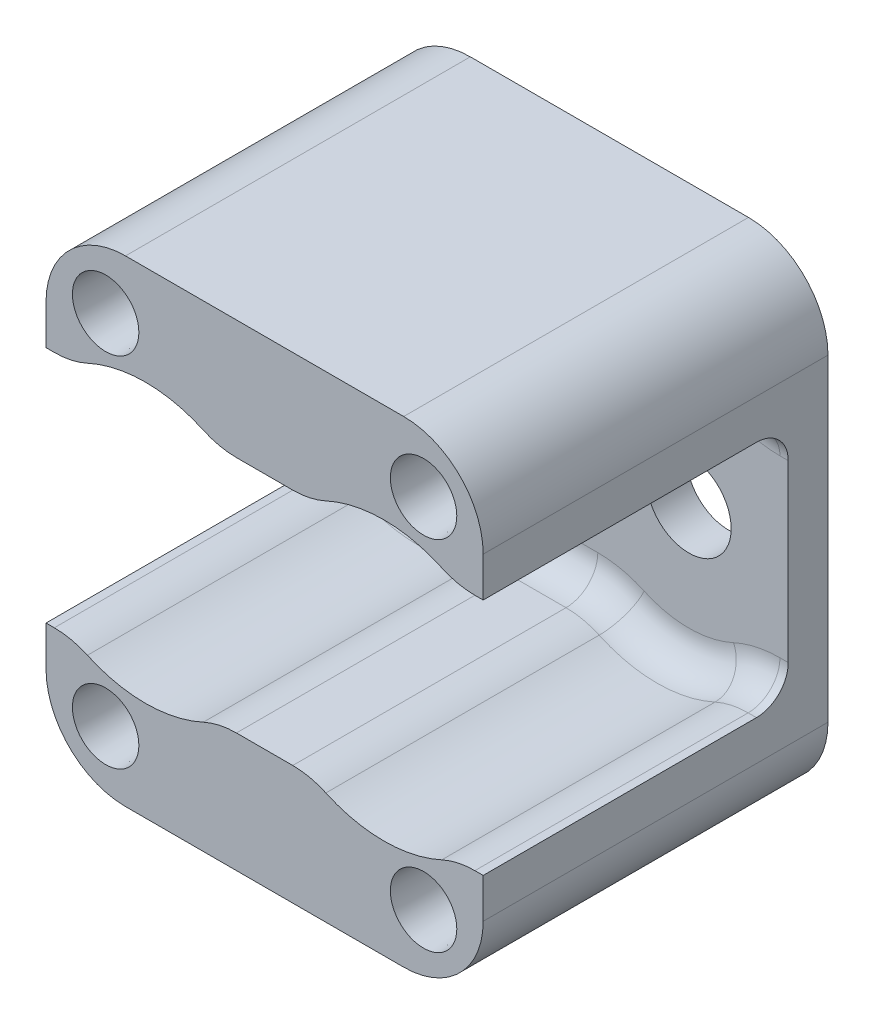
SolidWorks part; units mm, degrees
material "PET"
ref_plane "Front Plane" through (0, 0, 0) normal (0, 0, 1) x (1, 0, 0)
ref_plane "Top Plane" through (0, 0, 0) normal (0, 1, 0) x (1, 0, 0)
ref_plane "Right Plane" through (0, 0, 0) normal (1, 0, 0) x (0, 0, -1)
sketch "Sketch1" plane through (0, 0, 0) normal (0, 0, 1) x (1, 0, 0)
  line L0 (-19.05, 0) -> (0, 0) construction
  line L2 (7.9375, -19.05) -> (-26.9875, -19.05)
  line L3 (7.9375, -19.05) -> (7.9375, 19.05)
  line L4 (7.9375, 19.05) -> (-26.9875, 19.05)
  line L5 (-26.9875, -19.05) -> (-26.9875, 19.05)
  line L6 (7.9375, -19.05) -> (-26.9875, 19.05) construction
  line L7 (7.9375, 19.05) -> (-26.9875, -19.05) construction
  point P4 (-9.525, 0)
  dimension "D1" = 34.925
  dimension "D2" = 38.1
extrude "Boss-Extrude1" add sketch "Sketch1" along normal blind 3.175
sketch "Sketch2" plane through (0, 0, 3.175) normal (0, 0, 1) x (1, 0, 0)
  line L0 (7.9375, -19.05) -> (7.9375, 19.05) construction
  line L1 (-26.9875, 19.05) -> (7.9375, 19.05)
  line L2 (-26.9875, 19.05) -> (-26.9875, 9.525)
  line L3 (-26.9875, 9.525) -> (7.9375, 9.525)
  line L4 (7.9375, 19.05) -> (7.9375, 9.525)
  dimension "D1" = 9.525
extrude "Boss-Extrude2" add sketch "Sketch2" along normal up to surface (24.3713 mm away)
sketch "Sketch3" plane through (0, 0, 19.6088) normal (0, 0, 1) x (1, 0, 0)
  circle A0 centre (-19.05, 0) radius 11.1125
  circle A1 centre (0, 0) radius 11.1125
  dimension "D1" = 22.225
extrude "Cut-Extrude1" cut sketch "Sketch3" against normal up to surface (16.4338 mm away) and the other way through all contours A1 A0 | A0 A1 | A0 A1 region at (-9.525, 0, 19.6088) region at (0.6449, 0, 19.6088) region at (-19.6949, 0, 19.6088) up to face at (-13.8906, -4.7625, 3.175)
mirror "Mirror1" about plane through (0, 0, 0) normal (0, 1, 0) of "Cut-Extrude1", "Boss-Extrude2"
fillet "Fillet1" radius 6.35 12 edges at (7.9375, 19.05, 13.7732) (-26.9875, 19.05, 13.7732) (5.7238, 9.525, 15.3607) (-5.7238, 9.525, 15.3607) (-13.3262, 9.525, 15.3607) (-24.7738, 9.525, 15.3607) (7.9375, -19.05, 13.7732) (-26.9875, -19.05, 13.7732) (5.7238, -9.525, 15.3607) (-5.7238, -9.525, 15.3607) (-13.3262, -9.525, 15.3607) (-24.7738, -9.525, 15.3607)
fillet "Fillet2" radius 2.54 18 edges at (5.921, 9.671, 3.175) (0, 11.1125, 3.175) (-5.921, 9.671, 3.175) (-13.129, 9.671, 3.175) (-19.05, 11.1125, 3.175) (-24.971, 9.671, 3.175) (7.6062, -9.525, 3.175) (5.921, -9.671, 3.175) (0, -11.1125, 3.175) (-5.921, -9.671, 3.175) (-9.525, -9.525, 3.175) (-13.129, -9.671, 3.175) (-19.05, -11.1125, 3.175) (-24.971, -9.671, 3.175) (-26.6562, -9.525, 3.175)
sketch "Sketch4" plane through (0, 0, 3.175) normal (0, 0, 1) x (1, 0, 0)
  line L0 (-19.05, 0) -> (-23.3706, 1.7896) construction
  line L1 (-22.5585, -3.2205) -> (-18.8463, -4.7581) construction
  line L2 (-19.8994, 4.7507) -> (-15.0902, 2.7586)
  line L3 (-15.5415, 3.2205) -> (-19.2537, 4.7581) construction
  line L4 (-19.05, 0) -> (-20.8968, -4.4586) construction
  arc A0 (-20.8968, -4.4586) -> (-15.0902, 2.7586) centre (-19.05, 0) ccw
  arc A1 (-19.8994, 4.7507) -> (-20.8968, -4.4586) centre (-19.05, 0) ccw
  dimension "D1" = 9.652
  dimension "D2" = 8.89
extrude "Cut-Extrude2" cut sketch "Sketch4" against normal through all
hole_wizard "1/4 Clearance Hole1" positions "Sketch6" profile "Sketch5" hole size "1/4" standard "ANSI Inch" end condition through all
sketch "Sketch6" plane through (0, 0, 3.175) normal (0, 0, 1) x (1, 0, 0)
  point P0 (0, 0)
sketch "Sketch5" plane through (0, 0, 3.175) normal (1, 0, 0) x (0, -1, 0)
  line L0 (0, 0) -> (0, 3.175)
  line L1 (0, 3.175) -> (3.3782, 3.175)
  line L2 (3.3782, 3.175) -> (3.3782, 0)
  line L5 (3.3782, 0) -> (0, 0)
  line L11 (0, -6.35) -> (0, 107.95) construction
  dimension "Thru Hole Dia." = 6.7564
  dimension "Thru Hole Depth" = 3.175
hole_wizard "#6 Clearance Hole1" positions "Sketch8" profile "Sketch7" hole size "#6" standard "ANSI Inch" end condition through all
sketch "Sketch8" plane through (0, 0, 0) normal (0, 0, -1) x (-1, 0, 0)
  line L0 (-7.9375, -12.7) -> (-7.9375, 12.7) construction
  line L1 (-1.5875, 19.05) -> (20.6375, 19.05) construction
  line L2 (9.525, 19.05) -> (9.525, 0) construction
  line L3 (9.525, 0) -> (26.9875, 0) construction
  line L4 (26.9875, 12.7) -> (26.9875, -12.7) construction
  point P0 (-3.175, 14.2875)
  point P21 (22.225, 14.2875)
  point P23 (22.225, -14.2875)
  point P24 (-3.175, -14.2875)
  dimension "D1" = 4.7625
  dimension "D2" = 4.7625
sketch "Sketch7" plane through (3.175, 14.2875, 0) normal (1, 0, 0) x (0, 1, 0)
  line L0 (0, 0) -> (0, 27.5463)
  line L1 (0, 27.5463) -> (2.1526, 27.5463)
  line L2 (2.1526, 27.5463) -> (2.1526, 0)
  line L5 (2.1526, 0) -> (0, 0)
  line L11 (0, -6.35) -> (0, 107.95) construction
  dimension "Thru Hole Dia." = 4.3053
  dimension "Thru Hole Depth" = 27.5463
hole_wizard "Hole1" positions "Sketch10" profile "Sketch9" legacy
sketch "Sketch10" plane through (0, 0, 27.5463) normal (0, 0, 1) x (1, 0, 0)
  point P0 (-22.225, 14.2875)
  point P3 (3.175, 14.2875)
  point P6 (-22.225, -14.2875)
  point P9 (3.175, -14.2875)
sketch "Sketch9" plane through (-22.225, 14.2875, 27.5463) normal (1, 0, 0) x (0, -1, 0)
  line L0 (0, 0) -> (0, 3.81)
  line L1 (0, 3.81) -> (2.5273, 3.81)
  line L2 (2.5273, 3.81) -> (2.6543, 0)
  line L3 (2.6543, 0) -> (0, 0)
  line L4 (0, 110) -> (0, -10) construction
  dimension "Minor Diameter" = 5.0546
  dimension "Depth" = 3.81
  dimension "Major Diameter" = 5.3086
